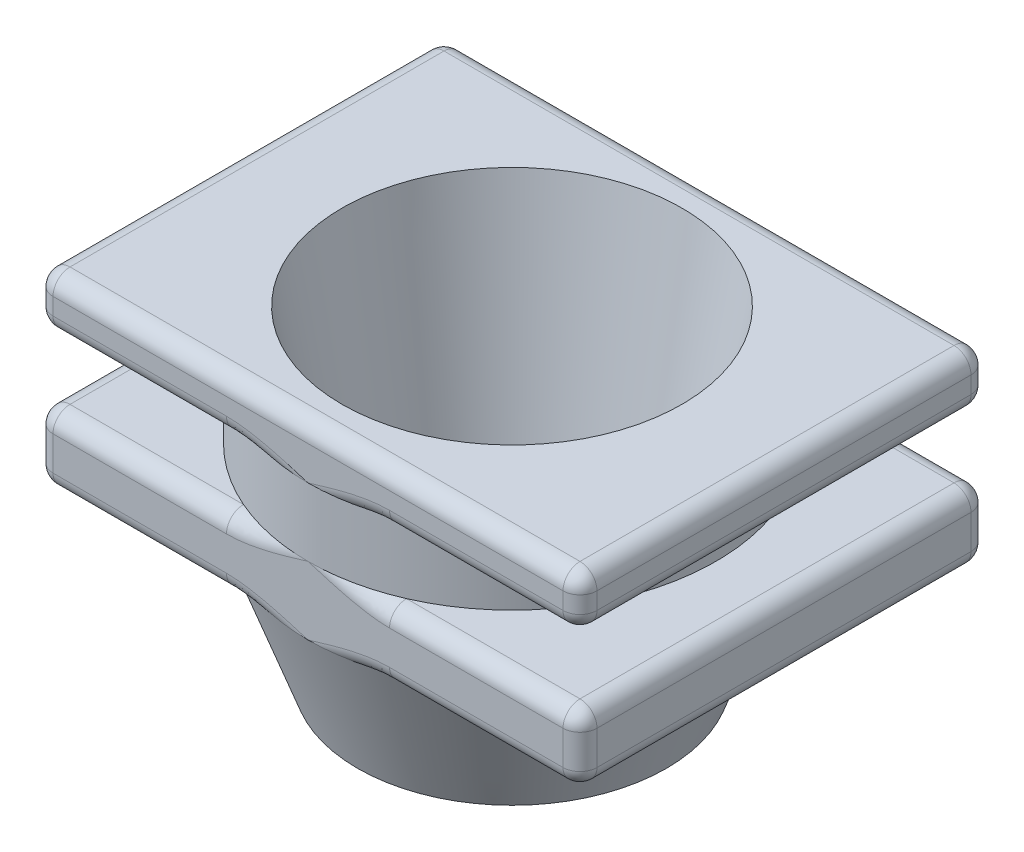
SolidWorks part; units mm, degrees
ref_plane "Front Plane" through (0, 0, 0) normal (0, 0, 1) x (1, 0, 0)
ref_plane "Top Plane" through (0, 0, 0) normal (0, 1, 0) x (1, 0, 0)
ref_plane "Right Plane" through (0, 0, 0) normal (1, 0, 0) x (0, 0, -1)
sketch "Sketch1" plane through (0, 0, 0) normal (0, 1, 0) x (1, 0, 0)
  circle A0 centre (0, 0) radius 60
  dimension "D1" = 120
extrude "Boss-Extrude1" add sketch "Sketch1" along normal blind 20
sketch "Sketch2" plane through (0, 20, 0) normal (0, 1, 0) x (1, 0, 0)
  line L2 (60, 0) -> (60, 60)
  line L3 (60, 60) -> (0, 60)
  line L5 (0, -60) -> (-60, -60)
  line L8 (-60, -60) -> (-60, 0)
  line L9 (-60, -60) -> (60, -60)
  line L10 (-60, -60) -> (-60, 60)
  line L11 (-60, 60) -> (60, 60)
  line L12 (60, -60) -> (60, 60)
  point P0 (60, 0)
  point P1 (0, 60)
  point P2 (0, 0)
  point P8 (0, -60)
  point P9 (-60, 0)
  circle M2 centre (0, 0) radius 60
extrude "Boss-Extrude2" add sketch "Sketch2" along normal blind 15 contours L2 L3 M2 | M2 | L11 L10 M2 | L8 L5 M2 | L9 L12 M2
sketch "Sketch3" plane through (0, 0, 0) normal (0, -1, 0) x (1, 0, 0)
  line L0 (-60, 60) -> (-60, 0) construction
  line L1 (0, 60) -> (-60, 60) construction
  line L2 (-60, -60) -> (0, -60) construction
  line L3 (-60, 0) -> (-60, -60) construction
  line L4 (60, -60) -> (60, 0) construction
  line L5 (0, -60) -> (60, -60) construction
  line L6 (60, 60) -> (0, 60) construction
  line L7 (60, 0) -> (60, 60) construction
  line L8 (-60, 60) -> (-60, 0)
  line L9 (0, 60) -> (-60, 60)
  line L10 (-60, -60) -> (0, -60)
  line L11 (-60, 0) -> (-60, -60)
  line L12 (60, -60) -> (60, 0)
  line L13 (0, -60) -> (60, -60)
  line L14 (60, 60) -> (0, 60)
  line L15 (60, 0) -> (60, 60)
  arc A0 (0, 60) -> (-60, 0) centre (0, 0) ccw construction
  arc A1 (-60, 0) -> (0, -60) centre (0, 0) ccw construction
  arc A2 (0, -60) -> (60, 0) centre (0, 0) ccw construction
  arc A3 (60, 0) -> (0, 60) centre (0, 0) ccw construction
  arc A4 (0, 60) -> (-60, 0) centre (0, 0) ccw
  arc A5 (-60, 0) -> (0, -60) centre (0, 0) ccw
  arc A6 (0, -60) -> (60, 0) centre (0, 0) ccw
  arc A7 (60, 0) -> (0, 60) centre (0, 0) ccw
  circle M1 centre (0, 0) radius 60
extrude "Boss-Extrude3" add sketch "Sketch3" along normal blind 20 contours L15 L14 M1 | L13 L12 M1 | M1 | L11 L10 M1 | L9 L8 M1
sketch "Sketch4" plane through (0, -20, 0) normal (0, -1, 0) x (1, 0, 0)
  arc A0 (0, -60) -> (60, 0) centre (0, 0) ccw construction
  arc A1 (-60, 0) -> (0, -60) centre (0, 0) ccw construction
  arc A2 (60, 0) -> (0, 60) centre (0, 0) ccw construction
  arc A3 (0, 60) -> (-60, 0) centre (0, 0) ccw construction
  arc A4 (0, -60) -> (60, 0) centre (0, 0) ccw
  arc A5 (-60, 0) -> (0, -60) centre (0, 0) ccw
  arc A6 (60, 0) -> (0, 60) centre (0, 0) ccw
  arc A7 (0, 60) -> (-60, 0) centre (0, 0) ccw
  circle A8 centre (0, 0) radius 60
extrude "Boss-Extrude4" add sketch "Sketch4" along normal blind 40 draft 20 contours A6 A7 A5 A4
sketch "Sketch5" plane through (60, 0, 0) normal (1, 0, 0) x (0, 0, -1)
  line L0 (-60, 20) -> (0, 20) construction
  line L1 (0, 20) -> (60, 20) construction
  line L2 (60, 20) -> (60, 35) construction
  line L3 (60, 35) -> (-60, 35) construction
  line L4 (-60, 35) -> (-60, 20) construction
  line L5 (60, 0) -> (0, 0) construction
  line L6 (0, 0) -> (-60, 0) construction
  line L7 (-60, 0) -> (-60, -20) construction
  line L8 (-60, -20) -> (0, -20) construction
  line L9 (0, -20) -> (60, -20) construction
  line L10 (60, -20) -> (60, 0) construction
  line L11 (-60, 20) -> (0, 20)
  line L12 (0, 20) -> (60, 20)
  line L13 (60, 20) -> (60, 35)
  line L14 (60, 35) -> (-60, 35)
  line L15 (-60, 35) -> (-60, 20)
  line L16 (60, 0) -> (0, 0)
  line L17 (0, 0) -> (-60, 0)
  line L18 (-60, 0) -> (-60, -20)
  line L19 (-60, -20) -> (0, -20)
  line L20 (0, -20) -> (60, -20)
  line L21 (60, -20) -> (60, 0)
extrude "Boss-Extrude5" add sketch "Sketch5" along normal blind 20 and the other way blind 140
fillet "Fillet1" radius 5 26 edges at (80, 27.5, -60) (-80, 27.5, -60) (-40, 20, -60) (-40, 20, 60) (-80, 27.5, 60) (80, 27.5, 60) (80, -10, 60) (-40, -20, 60) (-80, -10, 60) (-40, 0, 60) (40, 0, 60) (-80, -10, -60) (-40, -20, -60) (80, -10, -60) (40, 0, -60) (-40, 0, -60) (-80, 35, 0) (0, 35, -60) (80, 35, 0) (0, 35, 60) (80, 20, 0) (-80, 20, 0) (-80, 0, 0) (-80, -20, 0) (80, -20, 0) (80, 0, 0)
sketch "Sketch6" plane through (0, 35, 0) normal (0, 1, 0) x (1, 0, 0)
  circle A0 centre (0, 0) radius 50
extrude "Cut-Extrude1" cut sketch "Sketch6" against normal through all draft 10
